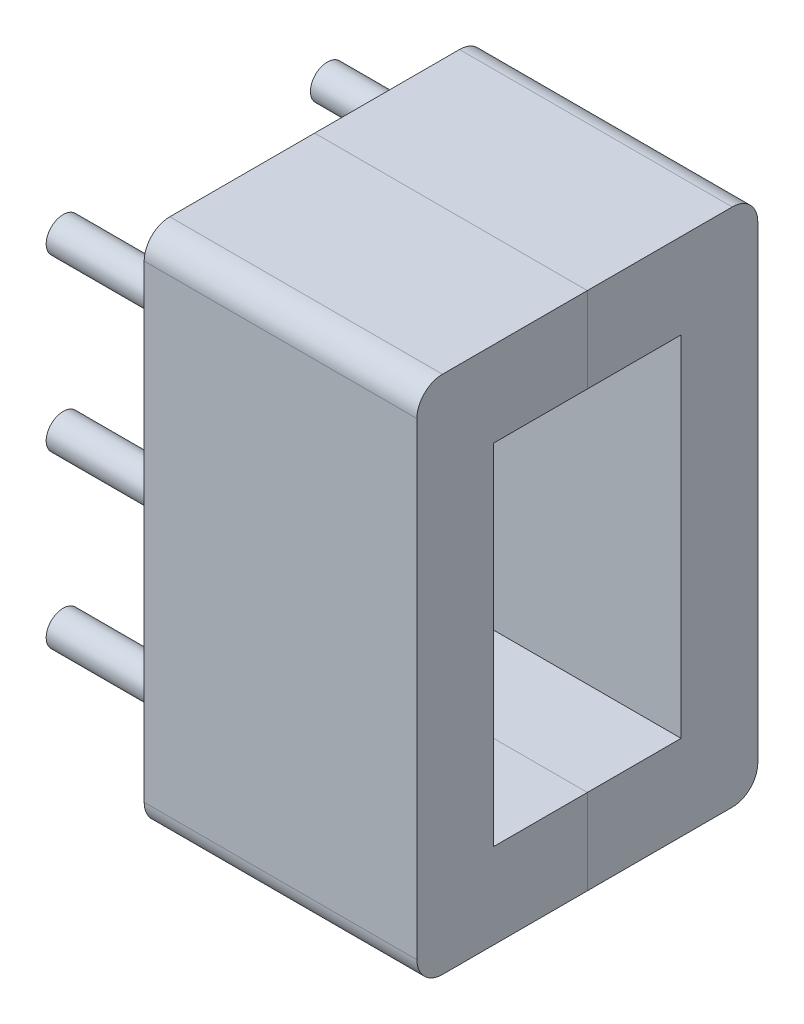
SolidWorks part; units mm, degrees
ref_plane "Alzado" through (0, 0, 0) normal (0, 0, 1) x (1, 0, 0)
ref_plane "Planta" through (0, 0, 0) normal (0, 1, 0) x (1, 0, 0)
ref_plane "Vista lateral" through (0, 0, 0) normal (1, 0, 0) x (0, 0, -1)
sketch "Croquis2" plane through (0, 0, 0) normal (1, 0, 0) x (0, 0, -1)
  line L0 (0, 24.489) -> (0, -53.3578) construction
  line L1 (5.835, 13.2874) -> (5.835, 12.9749) construction
  line L2 (10, 6.2874) -> (10, 3.7874) construction
  line L3 (5.835, -38.7126) -> (5.835, -38.4002) construction
  line L4 (5.835, -38.7126) -> (8, -38.7126) construction
  line L5 (9, -32.7126) -> (9, -37.7126) construction
  line L6 (10, -29.2126) -> (10, -31.7126) construction
  line L7 (5.835, 13.2874) -> (8, 13.2874) construction
  line L8 (9, 7.2874) -> (9, 12.2874) construction
  line L9 (6.5, 7.2874) -> (-6.5, 7.2874) construction
  line L10 (10, -29.2126) -> (10, 3.7874) construction
  line L11 (5.835, 13.2874) -> (5.835, 12.9749) construction
  line L12 (10, 6.2874) -> (10, 3.7874) construction
  line L13 (5.835, -38.7126) -> (5.835, -38.4002) construction
  line L14 (5.835, -38.7126) -> (8, -38.7126) construction
  line L15 (9, -32.7126) -> (9, -37.7126) construction
  line L16 (10, -29.2126) -> (10, -31.7126) construction
  line L17 (5.835, 13.2874) -> (8, 13.2874) construction
  line L18 (9, 7.2874) -> (9, 12.2874) construction
  line L19 (6.5, 7.2874) -> (-6.5, 7.2874) construction
  line L20 (10, -29.2126) -> (10, 3.7874) construction
  line L21 (-20, 17.7874) -> (20, 17.7874)
  line L22 (20, 17.7874) -> (20, -43.2126)
  line L24 (20, -43.2126) -> (-20, -43.2126)
  line L25 (-20, 17.7874) -> (-20, -43.2126)
  line L26 (-6.5, -32.7126) -> (6.5, -32.7126) construction
  line L27 (9, -32.7126) -> (6.5, -32.7126) construction
  line L28 (-6.5, -32.7126) -> (6.5, -32.7126) construction
  line L29 (9, -32.7126) -> (6.5, -32.7126) construction
  line L30 (-3, -33.7126) -> (-3, -32.7126) construction
  line L31 (3, -33.7126) -> (3, -32.7126) construction
  line L32 (-3, -33.7126) -> (-3, -32.7126) construction
  line L33 (3, -33.7126) -> (3, -32.7126) construction
  arc A0 (5.835, -38.4002) -> (4.335, -38.4002) centre (5.085, -36.3426) ccw construction
  arc A1 (4.335, 12.9749) -> (5.835, 12.9749) centre (5.085, 10.9174) ccw construction
  arc A2 (5.835, -38.4002) -> (4.335, -38.4002) centre (5.085, -36.3426) ccw construction
  arc A3 (4.335, 12.9749) -> (5.835, 12.9749) centre (5.085, 10.9174) ccw construction
  arc A4 (8, -38.7126) -> (9, -37.7126) centre (8, -37.7126) ccw construction
  arc A5 (9, -32.7126) -> (10, -31.7126) centre (9, -31.7126) ccw construction
  arc A6 (9, 12.2874) -> (8, 13.2874) centre (8, 12.2874) ccw construction
  arc A7 (10, 6.2874) -> (9, 7.2874) centre (9, 6.2874) ccw construction
  arc A8 (8, -38.7126) -> (9, -37.7126) centre (8, -37.7126) ccw construction
  arc A9 (9, -32.7126) -> (10, -31.7126) centre (9, -31.7126) ccw construction
  arc A10 (9, 12.2874) -> (8, 13.2874) centre (8, 12.2874) ccw construction
  arc A11 (10, 6.2874) -> (9, 7.2874) centre (9, 6.2874) ccw construction
  point P31 (0, -43.2126)
  point P33 (0, 17.7874)
  dimension "D1" = 4.5
  dimension "D2" = 10
  dimension "D3" = 4.5
extrude "Saliente-Extruir1" add sketch "Croquis2" against normal blind 32
sketch "Croquis4" plane through (0, 0, 0) normal (1, 0, 0) x (0, 0, -1)
  line L0 (3, -33.7126) -> (3, -32.7126) construction
  line L1 (-6.5, -32.7126) -> (6.5, -32.7126) construction
  line L2 (9, -32.7126) -> (6.5, -32.7126) construction
  line L3 (10, -29.2126) -> (10, -31.7126) construction
  line L4 (10, 6.2874) -> (10, 3.7874) construction
  line L5 (10, -29.2126) -> (10, 3.7874) construction
  line L6 (6.5, 7.2874) -> (-6.5, 7.2874) construction
  line L7 (0, 24.489) -> (0, -53.3578) construction
  line L8 (3, -33.7126) -> (3, -32.7126) construction
  line L9 (-6.5, -32.7126) -> (6.5, -32.7126) construction
  line L10 (9, -32.7126) -> (6.5, -32.7126) construction
  line L11 (10, -29.2126) -> (10, -31.7126) construction
  line L12 (10, 6.2874) -> (10, 3.7874) construction
  line L13 (10, -29.2126) -> (10, 3.7874) construction
  line L14 (6.5, 7.2874) -> (-6.5, 7.2874) construction
  line L15 (0, 24.489) -> (0, -53.3578) construction
  line L16 (-11, 7.7874) -> (11, 7.7874)
  line L17 (11, 7.7874) -> (11, -33.2126)
  line L19 (-11, 7.7874) -> (-11, -33.2126)
  line L35 (3, -33.7126) -> (2.5, -34.2126) construction
  line L43 (11, -33.2126) -> (-11, -33.2126)
  arc A0 (9, -32.7126) -> (10, -31.7126) centre (9, -31.7126) ccw construction
  arc A1 (9, -32.7126) -> (10, -31.7126) centre (9, -31.7126) ccw construction
  point P14 (0, -33.2126)
  point P20 (0, 7.7874)
  point P22 (0, -43.2126)
  dimension "D1" = 0.5
  dimension "D2" = 1
  dimension "D3" = 0.5
  dimension "D8" = 0.5
  dimension "D9" = 2.5
extrude "Cortar-Extruir1" cut sketch "Croquis4" against normal through all both and the other way through all
sketch "Croquis5" plane through (-32, 0, 0) normal (-1, 0, 0) x (0, 0, 1)
  line L0 (-9, 7.2874) -> (-9, 12.2874) construction
  line L1 (-9, -32.7126) -> (-9, -37.7126) construction
  line L2 (-5.835, -38.7126) -> (-8, -38.7126) construction
  line L3 (-5.835, 13.2874) -> (-8, 13.2874) construction
  line L4 (-9, 7.2874) -> (-9, 12.2874) construction
  line L5 (-9, -32.7126) -> (-9, -37.7126) construction
  line L6 (-5.835, -38.7126) -> (-8, -38.7126) construction
  line L7 (-5.835, 13.2874) -> (-8, 13.2874) construction
  line L8 (0, 24.489) -> (0, -53.3578) construction
  line L9 (0, 24.489) -> (0, -53.3578) construction
  line L10 (9.5, 13.7874) -> (-9.5, 13.7874)
  line L11 (-9.5, 13.7874) -> (-9.5, -39.2126)
  line L12 (-9.5, -39.2126) -> (9.5, -39.2126)
  line L13 (9.5, 13.7874) -> (9.5, -39.2126)
  arc A0 (-4.335, -38.4002) -> (-5.835, -38.4002) centre (-5.085, -36.3426) ccw construction
  arc A1 (-5.835, 12.9749) -> (-4.335, 12.9749) centre (-5.085, 10.9174) ccw construction
  arc A2 (-4.335, -38.4002) -> (-5.835, -38.4002) centre (-5.085, -36.3426) ccw construction
  arc A3 (-5.835, 12.9749) -> (-4.335, 12.9749) centre (-5.085, 10.9174) ccw construction
  point P21 (0, -39.2126)
  point P22 (0, 13.7874)
  dimension "D1" = 0.5
  dimension "D2" = 0.5
  dimension "D3" = 0.5
extrude "Cortar-Extruir2" cut sketch "Croquis5" against normal blind 8 and the other way through all
sketch "Croquis7" plane through (-24, 0, 0) normal (-1, 0, 0) x (0, 0, 1)
  line L4 (-9.5, 7.7874) -> (9.5, 7.7874)
  line L5 (9.5, 7.7874) -> (9.5, 13.7874)
  line L6 (9.5, 13.7874) -> (-9.5, 13.7874)
  line L7 (-9.5, 13.7874) -> (-9.5, 7.7874)
  line L8 (-9.5, 7.7874) -> (9.5, 7.7874)
  line L9 (9.5, 7.7874) -> (9.5, 13.7874)
  line L10 (9.5, 13.7874) -> (-9.5, 13.7874)
  line L11 (-9.5, 13.7874) -> (-9.5, 7.7874)
  line L12 (9.5, -33.2126) -> (-9.5, -33.2126)
  line L13 (-9.5, -33.2126) -> (-9.5, -39.2126)
  line L14 (-9.5, -39.2126) -> (9.5, -39.2126)
  line L15 (9.5, -39.2126) -> (9.5, -33.2126)
  line L16 (9.5, -33.2126) -> (-9.5, -33.2126)
  line L17 (-9.5, -33.2126) -> (-9.5, -39.2126)
  line L18 (-9.5, -39.2126) -> (9.5, -39.2126)
  line L19 (9.5, -39.2126) -> (9.5, -33.2126)
  dimension "D1" = 0
  dimension "D2" = 0
extrude "Saliente-Extruir2" add sketch "Croquis7" along normal up to surface (8 mm away) from offset 1.5 up to face at (-32, -12.7126, 0)
sketch "Croquis9" plane through (-32, 0, 0) normal (1, 0, 0) x (0, 0, -1)
  line L0 (-15.5, 3.7699) -> (-15.5, -40.0796) construction
  line L2 (100, 3.7699) -> (-100, 3.7699) construction
  line L3 (100, 12.7699) -> (-100, 12.7699) construction
  line L4 (-20, 17.7874) -> (-20, -43.2126) construction
  line L5 (-11, -33.2126) -> (-11, 7.7874) construction
  line L6 (-20, 17.7874) -> (-20, -43.2126) construction
  line L7 (-11, -33.2126) -> (-11, 7.7874) construction
  line L8 (0, 24.489) -> (0, -53.3578) construction
  line L9 (0, 24.489) -> (0, -53.3578) construction
  line L10 (-20, 6.2236) -> (-11, 6.2236) construction
  line L11 (-15.5, 3.7699) -> (-15.5, 12.7699) construction
  circle A0 centre (-15.5, 8.2699) radius 2
  circle A1 centre (-15.5, -31.7301) radius 2
  circle A2 centre (-15.5, -11.7301) radius 2
  circle A3 centre (15.5, -31.7301) radius 2
  circle A4 centre (15.5, -11.7301) radius 2
  circle A5 centre (15.5, 8.2699) radius 2
  point P14 (-15.5, 6.2236)
  dimension "D1" = 40
  dimension "D2" = 20
  dimension "D3" = 4
extrude "Saliente-Extruir3" add sketch "Croquis9" against normal blind 14
fillet "Redondeo1" radius 3 4 edges at (-16, -43.2126, 20) (-16, -43.2126, -20) (-16, 17.7874, -20) (-16, 17.7874, 20)
sketch "Croquis10" plane through (0, 0, 20) normal (0, 0, 1) x (1, 0, 0)
  line L0 (0, 14.7874) -> (-32, 14.7874) construction
  line L1 (0, 14.7874) -> (-32, 14.7874) construction
split "Partir1" trim tools "Alzado" bodies to split 108 resulting bodies 106 107
